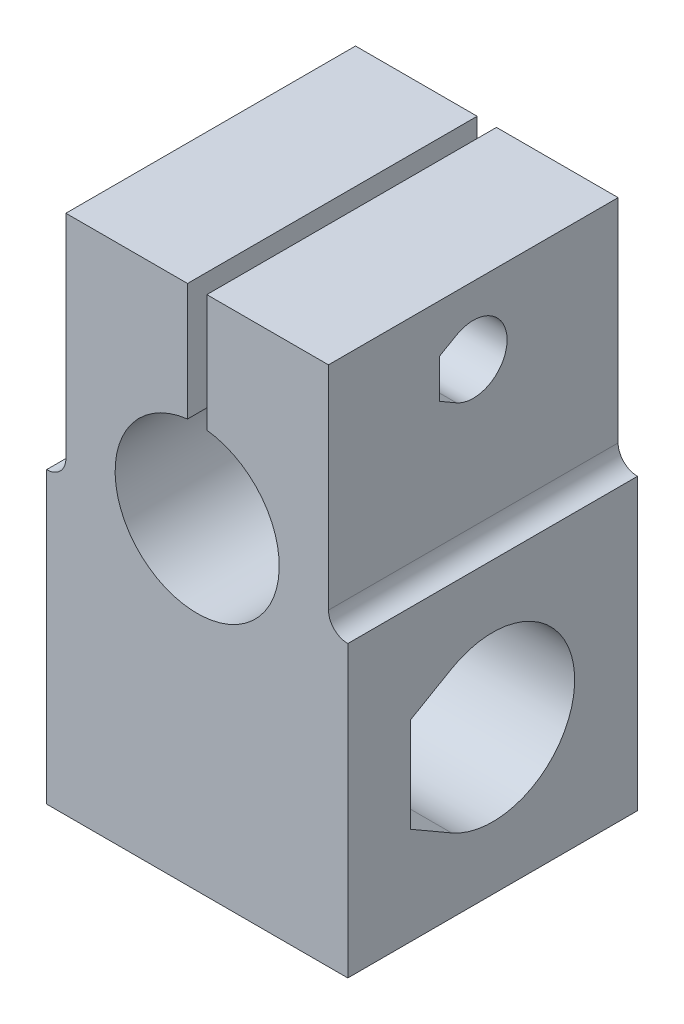
SolidWorks part; units mm, degrees
ref_plane "Piano frontale" through (0, 0, 0) normal (0, 0, 1) x (1, 0, 0)
ref_plane "Piano superiore" through (0, 0, 0) normal (0, 1, 0) x (1, 0, 0)
ref_plane "Piano destro" through (0, 0, 0) normal (1, 0, 0) x (0, 0, -1)
sketch "Schizzo1" plane through (0, 0, 0) normal (0, 0, 1) x (1, 0, 0)
  line L0 (-7.8, 0) -> (-7.8, 15)
  line L1 (-7.8, 15) -> (-6.8, 15)
  line L2 (-6.8, 15) -> (-6.8, 27)
  line L3 (-6.8, 27) -> (-0.5, 27)
  line L4 (-0.5, 27) -> (-0.5, 20.9205)
  line L5 (0.5, 27) -> (0.5, 20.9205)
  line L6 (0.5, 27) -> (6.8, 27)
  line L7 (6.8, 27) -> (6.8, 15)
  line L8 (6.8, 15) -> (7.8, 15)
  line L9 (7.8, 15) -> (7.8, 0)
  line L10 (7.8, 0) -> (-7.8, 0)
  line L11 (0, 0) -> (0, 37.7654) construction
  line L12 (-7.8, 7.5) -> (7.8, 7.5) construction
  arc A62 (-0.5, 20.9205) -> (0.5, 20.9205) centre (0, 16.7) ccw
  dimension "D3" = 8.5
  dimension "D5" = 12
  dimension "D8" = 9.2
  dimension "D1" = 15
  dimension "D2" = 1
  dimension "D6" = 15.6
  dimension "D7" = 1
extrude "Main body" add sketch "Schizzo1" along normal mid plane 15 contours L5 A62 L4 L3 L2 L1 L0 L10 L9 L8 L7 L6
sketch "Schizzo2" plane through (6.8, 0, 0) normal (1, 0, 0) x (0, 0, -1)
  line L0 (-7.5, 27) -> (7.5, 27) construction
  line L1 (-7.5, 27) -> (7.5, 27)
  line L2 (0, 27) -> (0, 23.5) construction
  line L3 (-1.75, 22.4896) -> (-1.75, 24.5104)
  line L4 (-1.75, 24.5104) -> (-0.875, 25.0155)
  line L5 (-1.75, 22.4896) -> (-0.875, 21.9845)
  arc A0 (-0.875, 21.9845) -> (-0.875, 25.0155) centre (0, 23.5) ccw
  point P9 (-1.75, 23.5)
  dimension "D1" = 3.5
  dimension "D2" = 120
  dimension "D3" = 3.5
extrude "Screw" cut sketch "Schizzo2" against normal through all both and the other way through all contours A0 L4 L3 L5
sketch "Schizzo6" plane through (-6.8, 0, 0) normal (-1, 0, 0) x (0, 0, 1)
  line L1 (3.25, 23.5) -> (1.625, 26.3146)
  line L2 (1.625, 26.3146) -> (-1.625, 26.3146)
  line L3 (-1.625, 26.3146) -> (-3.25, 23.5)
  line L4 (-3.25, 23.5) -> (-1.625, 20.6854)
  line L5 (-1.625, 20.6854) -> (1.625, 20.6854)
  line L6 (1.625, 20.6854) -> (3.25, 23.5)
  circle A0 centre (0, 23.5) radius 2.8146 construction
  dimension "D1" = 6.5
extrude "Nut recess" cut sketch "Schizzo6" against normal blind 2.4
sketch "Schizzo7" plane through (-7.8, 0, 0) normal (-1, 0, 0) x (0, 0, 1)
  line L0 (-7.5, 15) -> (7.5, 0) construction
  line L1 (4.25, 5.0463) -> (4.25, 9.9537)
  line L2 (4.25, 9.9537) -> (2.125, 11.1806)
  line L3 (4.25, 5.0463) -> (2.125, 3.8194)
  arc A0 (2.125, 11.1806) -> (2.125, 3.8194) centre (0, 7.5) ccw
  point P9 (4.25, 7.5)
  dimension "D1" = 8.5
extrude "Bar hole" cut sketch "Schizzo7" against normal through all
fillet "Relief 1" radius 1 1 edges at (6.8, 15, 0)
fillet "Relief 2" radius 1 1 edges at (-6.8, 15, 0)
ref_axis "Bar axis" through (7.8, 7.5, 0) along (-1, 0, 0)
ref_axis "Rod axis" through (0, 16.7, 7.5) along (0, 0, -1)
ref_axis "Rod clamp axis" through (0.5, 23.5, 0) along (1, 0, 0)
